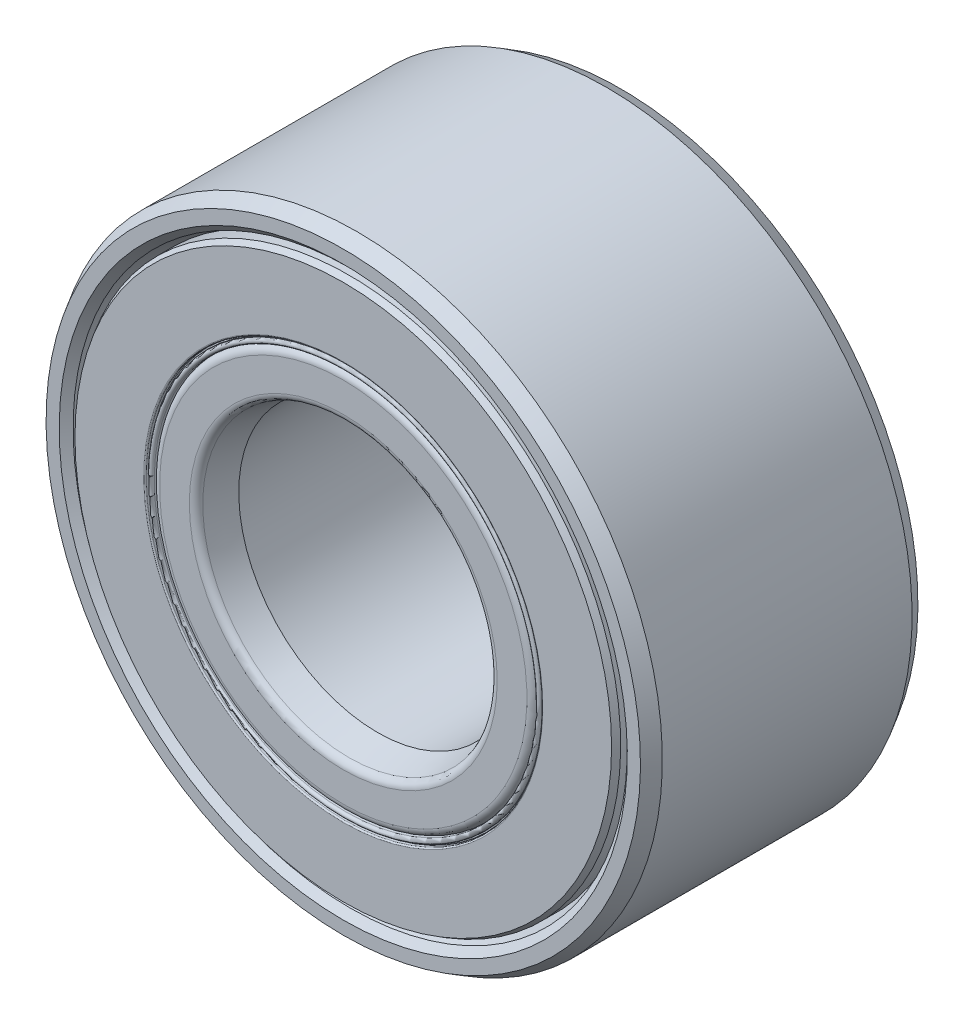
SolidWorks part; units mm, degrees
ref_plane "Front Plane" through (0, 0, 0) normal (0, 0, 1) x (1, 0, 0)
ref_plane "Top Plane" through (0, 0, 0) normal (0, 1, 0) x (1, 0, 0)
ref_plane "Right Plane" through (0, 0, 0) normal (1, 0, 0) x (0, 0, -1)
sketch "Sketch1" plane through (0, 0, 0) normal (0, 0, 1) x (1, 0, 0)
  line L0 (-5.5, 0) -> (5.5, 0) construction
  line L1 (-2.5, 0) -> (2.5, 0) construction
  circle A0 centre (0, 0) radius 2.5 construction
  circle A1 centre (0, 0) radius 5.5 construction
  point P3 (0, 0)
  point P6 (0, 0)
  point P7 (0, -2.5)
  point P11 (0, -5.5)
  point P12 (0, 2.5)
  point P13 (0, 5.5)
  dimension "OD" = 11
  dimension "ID" = 5
sketch "Sketch2" plane through (0, 0, 0) normal (1, 0, 0) x (0, 0, -1)
  line L0 (-2.5, 5.5) -> (2.5, 5.5) construction
  line L1 (0, 5.5) -> (0, -5.5) construction
  line L2 (2.25, 5.5) -> (-2.25, 5.5)
  line L3 (-2.25, 5.5) -> (-2.5, 5.3557)
  line L4 (-2.5, 5.3557) -> (-2.5, 5.1187)
  line L5 (-2.1037, 4.895) -> (-0.863, 4.895)
  line L6 (2.1037, 4.895) -> (0.863, 4.895)
  line L7 (2.5, 5.3557) -> (2.5, 5.1187)
  line L8 (2.25, 5.5) -> (2.5, 5.3557)
  line L9 (-0.863, 4.895) -> (-0.863, 5.0967) construction
  line L10 (-0.863, 5.0967) -> (-0.863, 5.2983) construction
  line L11 (0, 5.5) -> (0, -5.5) construction
  line L12 (-2.5, 0) -> (2.5, 0) construction
  line L13 (2.5, 2.5) -> (-2.5, 2.5) construction
  line L14 (-2.5, 2.5) -> (-2.5, -2.5) construction
  line L15 (-2.5, -2.5) -> (2.5, -2.5) construction
  line L16 (2.5, 5.5) -> (2.5, -5.5) construction
  line L17 (-0.863, 5.2983) -> (-0.863, 5.5) construction
  line L18 (-0.863, 5.2983) -> (0, 5.2983) construction
  line L20 (-2.1037, 4.895) -> (-2.375, 4.9937)
  line L21 (-2.375, 4.9937) -> (-2.5, 5.1187)
  line L26 (2.375, 4.9937) -> (2.5, 5.1187)
  line L27 (2.1037, 4.895) -> (2.375, 4.9937)
  arc A0 (-0.863, 4.895) -> (0.863, 4.895) centre (0, 4.1733) cw
  circle A1 centre (0, 4.1733) radius 1.125 construction
  point P17 (0, 0)
  point P21 (0, 5.5)
  point P30 (0, -2.5)
  dimension "Approx. Ball Dia." = 2.25
  dimension "Width" = 5
  dimension "For Shaft Diameter" = 5
  dimension "For Housing ID" = 11
  dimension "D4" = 9.79
  dimension "D2" = 20
  dimension "D5" = 45
  dimension "D1" = 30
  dimension "D6" = 0.25
  dimension "D7" = 0.125
sketch "Sketch3" plane through (0, 0, 0) normal (1, 0, 0) x (0, 0, -1)
  line L14 (-2.1037, 4.895) -> (-2.375, 4.9937) construction
  line L15 (-2.375, 4.9937) -> (-2.5, 5.1187) construction
  line L16 (-2.5, 5.3557) -> (-2.5, 5.1187) construction
  line L17 (-2.25, 5.5) -> (-2.5, 5.3557) construction
  line L18 (2.25, 5.5) -> (-2.25, 5.5) construction
  line L19 (2.25, 5.5) -> (2.5, 5.3557) construction
  line L20 (2.5, 5.3557) -> (2.5, 5.1187) construction
  line L21 (2.375, 4.9937) -> (2.5, 5.1187) construction
  line L22 (2.1037, 4.895) -> (2.375, 4.9937) construction
  line L23 (2.1037, 4.895) -> (0.863, 4.895) construction
  line L24 (-2.1037, 4.895) -> (-0.863, 4.895) construction
  line L25 (-2.1037, 4.895) -> (-2.375, 4.9937)
  line L26 (-2.375, 4.9937) -> (-2.5, 5.1187)
  line L27 (-2.5, 5.3557) -> (-2.5, 5.1187)
  line L28 (-2.25, 5.5) -> (-2.5, 5.3557)
  line L29 (2.25, 5.5) -> (-2.25, 5.5)
  line L30 (2.25, 5.5) -> (2.5, 5.3557)
  line L31 (2.5, 5.3557) -> (2.5, 5.1187)
  line L32 (2.375, 4.9937) -> (2.5, 5.1187)
  line L33 (2.1037, 4.895) -> (2.375, 4.9937)
  line L34 (2.1037, 4.895) -> (0.863, 4.895)
  line L35 (-2.1037, 4.895) -> (-0.863, 4.895)
  arc A2 (0.863, 4.895) -> (-0.863, 4.895) centre (0, 4.1733) ccw construction
  arc A3 (0.863, 4.895) -> (-0.863, 4.895) centre (0, 4.1733) ccw
revolve "Revolve1" add sketch "Sketch3" angle 360 about L12
sketch "Sketch4" plane through (0, 0, 0) normal (1, 0, 0) x (0, 0, -1)
  line L0 (0, 5.5) -> (0, -5.5) construction
  line L1 (0, 5.5) -> (0, -5.5) construction
  line L2 (-1.8832, 2.5) -> (-2.3948, 2.6371)
  line L3 (-2.5, 2.7742) -> (-2.5, 3.3097)
  line L4 (2.5, -5.3557) -> (2.5, 5.3557) construction
  line L5 (-2.3581, 3.4517) -> (-0.863, 3.4517)
  line L6 (-1.8832, 2.5) -> (1.8832, 2.5)
  line L7 (2.5, 5.3557) -> (2.5, 5.1187) construction
  line L8 (1.8832, 2.5) -> (2.3948, 2.6371)
  line L9 (0, 5.2983) -> (0, 2.5) construction
  line L10 (2.5, 2.7742) -> (2.5, 3.3097)
  line L11 (2.3581, 3.4517) -> (0.863, 3.4517)
  line L12 (1.8832, 2.5) -> (1.8832, 2.6371) construction
  line L13 (1.8832, 2.6371) -> (1.8832, 2.7742) construction
  line L14 (1.8832, 2.7742) -> (1.8832, 2.9112) construction
  line L15 (1.8832, 2.9112) -> (1.8832, 3.0483) construction
  circle A0 centre (0, 4.1733) radius 1.125 construction
  arc A1 (0.863, 3.4517) -> (-0.863, 3.4517) centre (0, 4.1733) cw
  arc A2 (2.5, 3.3097) -> (2.3581, 3.4517) centre (2.3581, 3.3097) ccw
  arc A3 (-2.5, 3.3097) -> (-2.3581, 3.4517) centre (-2.3581, 3.3097) cw
  arc A4 (2.3948, 2.6371) -> (2.5, 2.7742) centre (2.3581, 2.7742) ccw
  arc A5 (-2.3948, 2.6371) -> (-2.5, 2.7742) centre (-2.3581, 2.7742) cw
  point P14 (2.5, 2.6653)
  point P36 (0, 3.0483)
  dimension "D1" = 15
revolve "Revolve2" add sketch "Sketch4" angle 360 about L12
sketch "Sketch5" plane through (0, 0, 0) normal (1, 0, 0) x (0, 0, -1)
  line L0 (-1.125, 4.1733) -> (1.125, 4.1733)
  arc A2 (-1.125, 4.1733) -> (1.125, 4.1733) centre (0, 4.1733) cw
  arc A3 (0.863, 4.895) -> (-0.863, 4.895) centre (0, 4.1733) ccw construction
revolve "Revolve3" add sketch "Sketch5" angle 360 about L0
pattern_circular "CirPattern1" count 9 over 360 about axis through (0, 0, 2.5) along (0, 0, -1) of bodies 104
sketch "Sketch6" plane through (0, 0, 0) normal (1, 0, 0) x (0, 0, -1)
  line L1 (-2.3961, 4.895) -> (-1.125, 4.895)
  line L2 (-2.5, 4.835) -> (-2.5, 3.5957)
  line L3 (-2.476, 3.5717) -> (-1.125, 3.5717)
  line L4 (-1.125, 4.895) -> (-1.125, 3.5717)
  line L5 (-2.5, 2.7742) -> (-2.5, 3.3097) construction
  line L6 (-2.25, 5.5) -> (-2.5, 5.3557) construction
  line L7 (0, 5.5) -> (0, 2.5) construction
  line L8 (2.476, 3.5717) -> (1.125, 3.5717)
  line L9 (1.125, 4.895) -> (1.125, 3.5717)
  line L10 (2.3961, 4.895) -> (1.125, 4.895)
  line L11 (2.5, 4.835) -> (2.5, 3.5957)
  line L13 (-2.3581, 3.4517) -> (-0.863, 3.4517) construction
  line L14 (-2.5, 4.835) -> (-2.3961, 4.895)
  line L15 (-2.1037, 4.895) -> (-0.863, 4.895) construction
  line L16 (2.5, 4.835) -> (2.3961, 4.895)
  arc A0 (-2.5, 3.5957) -> (-2.476, 3.5717) centre (-2.476, 3.5957) ccw
  circle A1 centre (0, 4.1733) radius 1.125 construction
  arc A2 (2.5, 3.5957) -> (2.476, 3.5717) centre (2.476, 3.5957) cw
  point P26 (-2.5, 3.5717)
  dimension "D3" = 0.024
  dimension "D1" = 0.12
  dimension "D2" = 0.06
revolve "Revolve4" add sketch "Sketch6" angle 360 about L12
sketch "Sketch7" plane through (0, 0, 0) normal (1, 0, 0) x (0, 0, -1)
  line L3 (-1.125, 3.5717) -> (-2.4026, 3.5717)
  line L4 (-2.476, 3.5717) -> (-1.125, 3.5717) construction
  line L7 (0, 3.0483) -> (0, 2.5) construction
  line L8 (0, 5.5) -> (0, -5.5) construction
  line L21 (-2.4026, 3.5717) -> (-2.4322, 3.5665)
  line L22 (-2.43, 3.5417) -> (-2.455, 3.5417)
  line L23 (-2.455, 3.4517) -> (-1.125, 3.4517)
  line L24 (-1.125, 3.4517) -> (-1.125, 3.5717)
  line L25 (-2.3581, 3.4517) -> (-0.863, 3.4517) construction
  line L26 (-2.5, 3.5957) -> (-2.5, 3.4517) construction
  line L27 (-2.5, 3.4517) -> (-2.455, 3.4517) construction
  line L28 (-2.4026, 3.5717) -> (-2.4026, 3.5417) construction
  line L29 (-2.4026, 3.5417) -> (-2.4026, 3.5117) construction
  line L30 (-2.4026, 3.5117) -> (-2.4026, 3.4817) construction
  line L31 (-2.4026, 3.4817) -> (-2.4026, 3.4517) construction
  circle A2 centre (0, 4.1733) radius 1.125 construction
  arc A9 (-2.4322, 3.5665) -> (-2.43, 3.5417) centre (-2.43, 3.5542) ccw
  arc A10 (-2.455, 3.5417) -> (-2.455, 3.4517) centre (-2.455, 3.4967) ccw
  dimension "D1" = 0.025
  dimension "D2" = 10
revolve "Revolve5" add sketch "Sketch7" angle 360 about L12
equation "\"D4@Sketch2\"=\"OD@Sketch1\"*.89"
equation "\"D1@Sketch6\"=(\"OD@Sketch1\"-\"ID@Sketch1\")*.02"
equation "\"D2@Sketch6\"=\"D1@Sketch6\"*.5"
equation "\"D3@Sketch6\"=\"D1@Sketch6\"*.2"
equation "\"D6@Sketch2\"=\"Width@Sketch2\"*.05"
equation "\"D7@Sketch2\"=\"D6@Sketch2\"*.5"
equation "\"D1@CirPattern1\" =  ( pi * \"OD@Sketch1\" )  * .5625 / \"Approx. Ball Dia.@Sketch2\""
equation "\"Approx. Ball Dia.@Sketch2\"=(\"OD@Sketch1\"-\"ID@Sketch1\")*.5*.75"
